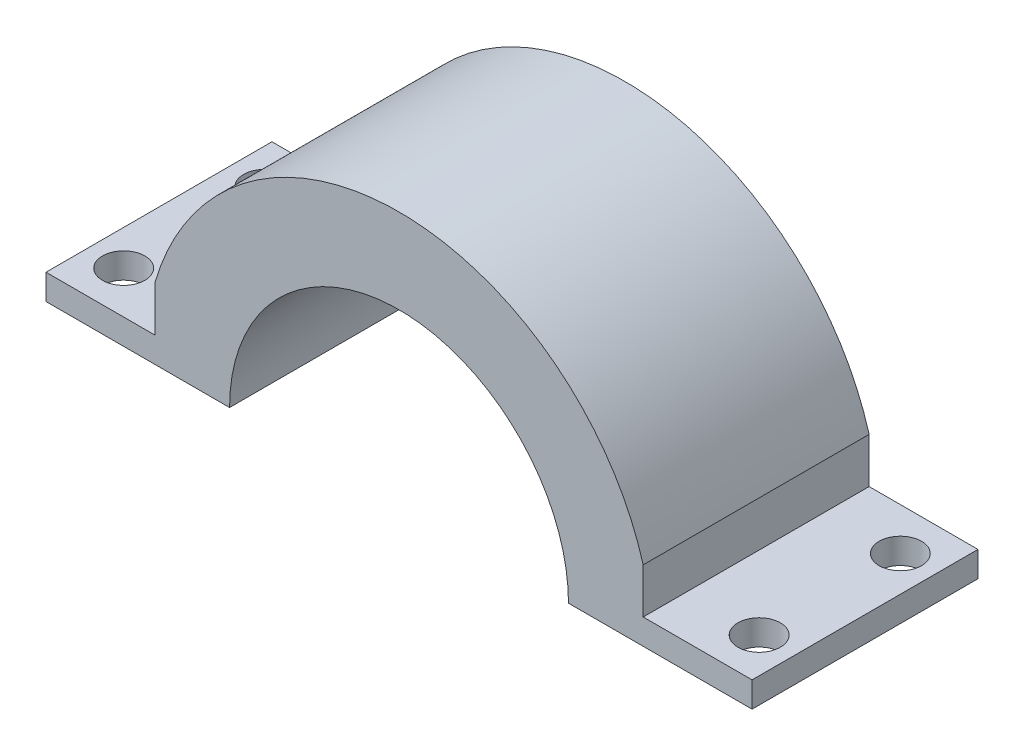
SolidWorks part; units mm, degrees
ref_plane "Front Plane" through (0, 0, 0) normal (0, 0, 1) x (1, 0, 0)
ref_plane "Top Plane" through (0, 0, 0) normal (0, 1, 0) x (1, 0, 0)
ref_plane "Right Plane" through (0, 0, 0) normal (1, 0, 0) x (0, 0, -1)
sketch "Sketch7" plane through (0, 0, 0) normal (0, 0, 1) x (1, 0, 0)
  line L17 (28.8688, -27.166) -> (28.8688, -22.166)
  line L20 (-21.1312, -22.166) -> (-21.1312, -27.166)
  line L24 (-21.1312, -27.166) -> (-8.1312, -27.166)
  line L25 (15.8688, -27.166) -> (28.8688, -27.166)
  line L28 (-13.4228, -22.166) -> (-21.1312, -22.166)
  line L29 (21.1604, -22.166) -> (28.8688, -22.166)
  line L30 (-21.1312, -27.166) -> (-8.1312, -27.166) construction
  arc A5 (-8.1312, -27.166) -> (15.8688, -27.166) centre (3.8688, -27.166) cw
  arc A6 (21.1604, -22.166) -> (-13.4228, -22.166) centre (3.8688, -27.166) ccw
  dimension "D3" = 13
  dimension "D4" = 50
  dimension "D2" = 12
  dimension "D1" = 13
  dimension "D7" = 5
  dimension "D8" = 5
extrude "Boss-Extrude1" add sketch "Sketch7" along normal blind 16
sketch "Sketch13" plane through (0, -22.166, 0) normal (0, 1, 0) x (1, 0, 0)
  line L42 (-13.4228, 0) -> (-21.1312, 0) construction
  line L43 (-21.1312, 0) -> (-13.4228, 0)
  line L44 (-21.1312, 0) -> (-21.1312, -16)
  line L45 (-21.1312, -16) -> (-13.4228, -16)
  line L46 (-13.4228, 0) -> (-13.4228, -16)
  line L48 (21.1604, 0) -> (28.8688, 0)
  line L49 (21.1604, 0) -> (21.1604, -16)
  line L50 (21.1604, -16) -> (28.8688, -16)
  line L51 (28.8688, 0) -> (28.8688, -16)
extrude "Cut-Extrude12" cut sketch "Sketch13" against normal blind 3.2 from surface starting at face at (25.0146, -22.166, 8)
sketch "Sketch14" plane through (0, -27.166, 0) normal (0, 1, 0) x (1, 0, 0)
  line L8 (28.8688, -16) -> (28.8688, 0) construction
  line L9 (15.8688, -16) -> (28.8688, -16) construction
  line L10 (15.8688, 0) -> (28.8688, 0) construction
  line L11 (-21.1312, 0) -> (-8.1312, 0) construction
  line L12 (-21.1312, -16) -> (-21.1312, 0) construction
  line L14 (-21.1312, -16) -> (-8.1312, -16) construction
  circle A0 centre (-18.6312, -3) radius 1.5
  circle A1 centre (-18.6312, -13) radius 1.5
  circle A2 centre (26.3688, -3) radius 1.5
  circle A3 centre (26.3688, -13) radius 1.5
  point P6 (0, 0)
  point P7 (0, 0)
  point P10 (0, 0)
  point P11 (0, 0)
  point P16 (0, 0)
  point P25 (-18.134, -13.1691)
  point P26 (-16.8592, -16)
  dimension "D1" = 2.5
  dimension "D2" = 3
  dimension "D3" = 3
  dimension "D4" = 2.5
  dimension "D5" = 3
  dimension "D6" = 2.5
  dimension "D7" = 2.5
  dimension "D8" = 3
extrude "Cut-Extrude13" cut sketch "Sketch14" along normal blind 50
